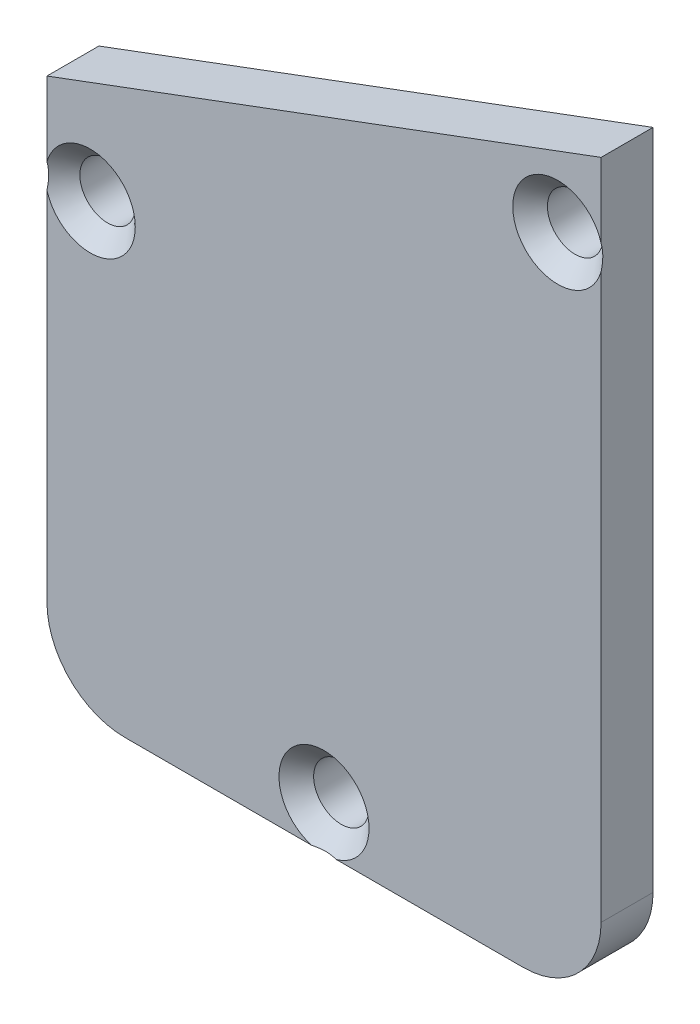
SolidWorks part; units mm, degrees
ref_plane "Płaszczyzna przednia" through (0, 0, 0) normal (0, 0, 1) x (1, 0, 0)
ref_plane "Płaszczyzna górna" through (0, 0, 0) normal (0, 1, 0) x (1, 0, 0)
ref_plane "Płaszczyzna prawa" through (0, 0, 0) normal (1, 0, 0) x (0, 0, -1)
sketch "Szkic1" plane through (0, 0, 0) normal (0, 0, 1) x (1, 0, 0)
  line L0 (16.7996, 22.6992) -> (-15.2004, 10.7692)
  line L2 (-15.2004, 10.7692) -> (-15.2004, -15.5608)
  line L3 (-10.7004, -20.0608) -> (12.2996, -20.0608)
  line L4 (16.7996, 22.6992) -> (16.7996, -15.5608)
  arc A0 (12.2996, -20.0608) -> (16.7996, -15.5608) centre (12.2996, -15.5608) ccw
  arc A1 (-15.2004, -15.5608) -> (-10.7004, -20.0608) centre (-10.7004, -15.5608) ccw
  dimension "D2" = 4.5
  dimension "D1" = 32
  dimension "D3" = 30.83
  dimension "D4" = 42.76
extrude "Dodanie-wyciągnięcie1" add sketch "Szkic1" along normal blind 3
sketch "Szkic2" plane through (0, 0, 3) normal (0, 0, 1) x (1, 0, 0)
  line L0 (-15.2004, 10.7692) -> (-15.2004, -15.5608) construction
  line L1 (16.7996, -15.5608) -> (16.7996, 22.6992) construction
  line L2 (-10.7004, -20.0608) -> (12.2996, -20.0608) construction
  circle A0 centre (-12.7004, 5.7692) radius 1.6
  circle A1 centre (14.2996, 17.6992) radius 1.6
  circle A2 centre (0.7996, -17.5608) radius 1.6
  point P12 (0, 0)
  point P13 (0.7996, -20.0608)
  dimension "D1" = 2.5
  dimension "D4" = 3.2
  dimension "D2" = 2.5
  dimension "D3" = 2.5
  dimension "D5" = 5
  dimension "D6" = 5
extrude "Wytnij-wyciągnięcie1" cut sketch "Szkic2" against normal blind 3
chamfer "Sfazowanie1" distance 1 angle 45 3 edges at (2.3996, -17.5608, 3) (15.8996, 17.6992, 3) (-11.1004, 5.7692, 3)
